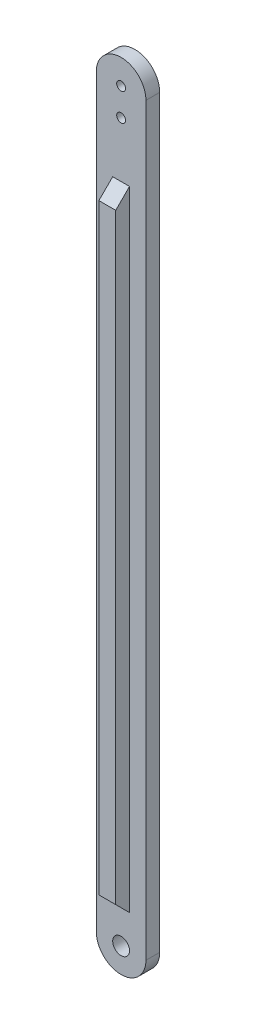
SolidWorks part; units mm, degrees
ref_plane "Front Plane" through (0, 0, 0) normal (0, 0, 1) x (1, 0, 0)
ref_plane "Top Plane" through (0, 0, 0) normal (0, 1, 0) x (1, 0, 0)
ref_plane "Right Plane" through (0, 0, 0) normal (1, 0, 0) x (0, 0, -1)
sketch "Sketch1" plane through (0, 0, 0) normal (0, 0, 1) x (1, 0, 0)
  line L0 (0, 270) -> (0, 0) construction
  line L1 (9, 270) -> (9, 0)
  line L2 (-9, 270) -> (-9, 0)
  arc A1 (9, 270) -> (-9, 270) centre (0, 270) ccw
  circle A2 centre (0, 0) radius 3.05
  arc A3 (-9, 0) -> (9, 0) centre (0, 0) ccw
  dimension "D1" = 270
  dimension "D3" = 9
  dimension "D2" = 18
extrude "Boss-Extrude1" add sketch "Sketch1" along normal blind 5
sketch "Sketch2" plane through (0, 0, 5) normal (0, 0, 1) x (1, 0, 0)
  line L0 (0, 270) -> (0, 260) construction
  circle A0 centre (0, 270) radius 1.6
  circle A1 centre (0, 260) radius 1.6
extrude "Cut-Extrude1" cut sketch "Sketch2" against normal blind 10
sketch "Sketch3" plane through (0, 0, 5) normal (0, 0, 1) x (1, 0, 0)
  line L0 (-3.05, 12) -> (-3.05, 240)
  line L2 (3.05, 12) -> (3.05, 240)
  line L3 (3.05, 240) -> (-3.05, 240)
  line L5 (0, 12) -> (3.05, 12)
  line L6 (0, 12) -> (-3.05, 12)
extrude "Boss-Extrude2" add sketch "Sketch3" along normal blind 5
chamfer "Chamfer1" distance 5 angle 45 2 edges at (0, 240, 10) (0, 12, 10)
